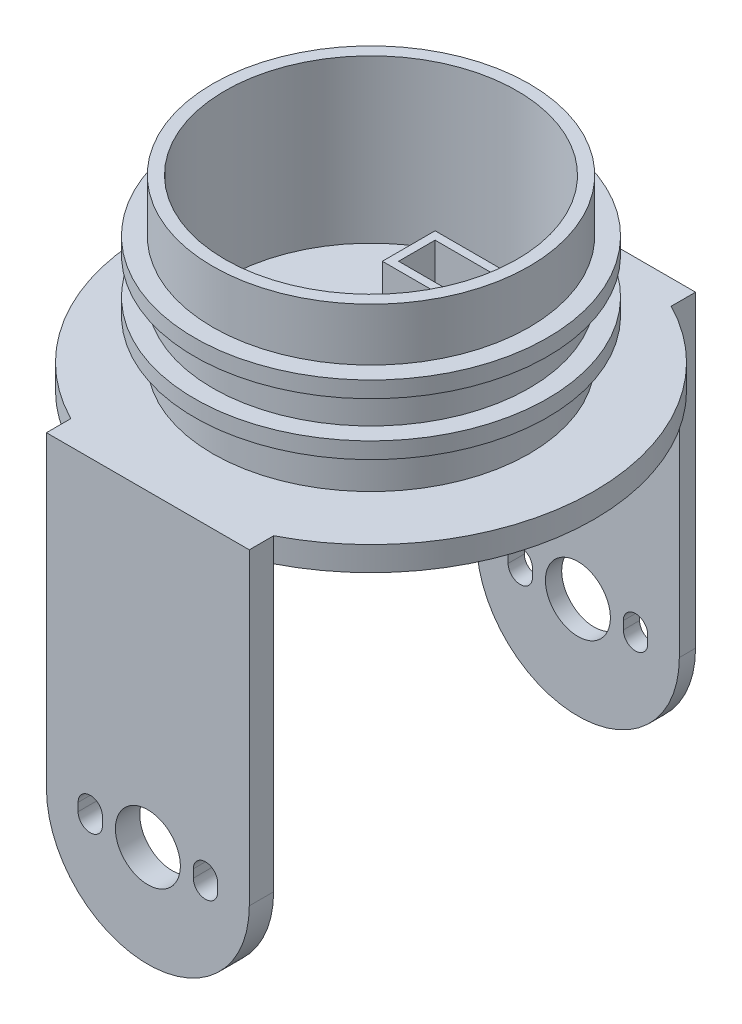
SolidWorks part; units mm, degrees
ref_plane "前基準面" through (0, 0, 0) normal (0, 0, 1) x (1, 0, 0)
ref_plane "上基準面" through (0, 0, 0) normal (0, 1, 0) x (1, 0, 0)
ref_plane "右基準面" through (0, 0, 0) normal (1, 0, 0) x (0, 0, -1)
sketch "草圖1" plane through (0, 0, 0) normal (0, 1, 0) x (1, 0, 0)
  circle A0 centre (0, 0) radius 19.5
  circle A1 centre (0, 0) radius 18
  dimension "D1" = 39
  dimension "D2" = 36
extrude "填料-伸長1" add sketch "草圖1" along normal blind 20
sketch "草圖3" plane through (0, 0, 0) normal (0, -1, 0) x (1, 0, 0)
  circle A0 centre (0, 0) radius 27.5
  dimension "D1" = 55
extrude "填料-伸長2" add sketch "草圖3" along normal blind 3
ref_plane "平面2" through (0, -3, 0) normal (0, -1, 0) x (-1, 0, 0)
ref_plane "平面5" through (0, 0, 0) normal (0, 1, 0) x (1, 0, 0)
ref_plane "平面6" through (0, 7, 0) normal (0, -1, 0) x (-1, 0, 0)
sketch "草圖25" plane through (0, 7, 0) normal (0, -1, 0) x (-1, 0, 0)
  circle A0 centre (0, 0) radius 21.75
  circle A1 centre (0, 0) radius 19.5
  dimension "D1" = 43.5
extrude "填料-伸長12" add sketch "草圖25" along normal blind 2
ref_plane "平面10" through (0, 10.5, 0) normal (0, -1, 0) x (-1, 0, 0)
sketch "草圖26" plane through (0, 10.5, 0) normal (0, -1, 0) x (-1, 0, 0)
  circle A0 centre (0, 0) radius 21.75
  circle A1 centre (0, 0) radius 19.5
extrude "填料-伸長13" add sketch "草圖26" against normal blind 2 from offset 1 offset against normal yes
sketch "草圖27" plane through (0, -3, 0) normal (0, -1, 0) x (1, 0, 0)
  line L0 (0, 0) -> (-12.5, 0)
  line L1 (46.0389, 0) -> (-46.0389, 0) construction
  line L2 (-12.5, 0) -> (-12.5, 25.5)
  line L3 (-12.5, 25.5) -> (12.5, 25.5)
  line L4 (12.5, 25.5) -> (12.5, 0)
  line L5 (12.5, 0) -> (-12.5, 0)
  line L6 (-12.5, 0) -> (-12.5, -25.5)
  line L7 (-12.5, -25.5) -> (12.5, -25.5)
  line L8 (12.5, -25.5) -> (12.5, 0)
  circle M6 centre (0, 0) radius 27.5
extrude "填料-伸長14" add sketch "草圖27" against normal blind 3 contours L8 L5 L0 L6 L7 M6 | L5 L4 L3 L2 L0 M6 | L6 L7 M6 | L7 L8 M6 | L4 L3 M6 | L3 L2 M6 region at (0, -3, -12.7084) region at (0, -3, 12.7084) region at (-11.7799, -3, 25.1714) region at (-11.7799, -3, -25.1714) region at (11.7799, -3, 25.1714) region at (11.7799, -3, -25.1714)
sketch "草圖28" plane through (0, 0, -25.5) normal (0, 0, -1) x (-1, 0, 0)
  line L0 (12.5, -3) -> (12.5, -38)
  line L1 (12.5, -38) -> (-12.5, -38)
  line L2 (-12.5, -38) -> (-12.5, 0)
  line L3 (-12.5, 0) -> (12.5, 0)
  line L4 (12.5, 0) -> (12.5, -3) construction
  line L5 (12.5, 0) -> (12.5, -3)
  line L6 (-7.1, -37.5) -> (-7.1, -38.5) construction
  line L7 (-5.6, -37.5) -> (-5.6, -38.5)
  line L8 (-8.6, -37.5) -> (-8.6, -38.5)
  line L9 (12.5, -3) -> (-12.5, -3)
  line L10 (7.1, -37.5) -> (7.1, -38.5) construction
  line L11 (8.6, -37.5) -> (8.6, -38.5)
  line L12 (5.6, -37.5) -> (5.6, -38.5)
  arc A0 (12.5, -38) -> (-12.5, -38) centre (0, -38) cw
  circle A1 centre (0, -38) radius 4
  arc A2 (-5.6, -37.5) -> (-8.6, -37.5) centre (-7.1, -37.5) ccw
  arc A3 (-8.6, -38.5) -> (-5.6, -38.5) centre (-7.1, -38.5) ccw
  arc A4 (8.6, -37.5) -> (5.6, -37.5) centre (7.1, -37.5) ccw
  arc A5 (5.6, -38.5) -> (8.6, -38.5) centre (7.1, -38.5) ccw
  point P14 (-7.1, -38)
  point P19 (-7.1, -36)
  point P20 (-7.1, -40)
  point P26 (7.1, -38)
  point P31 (7.1, -36)
  point P32 (7.1, -40)
  line M17 (10.2956, 0) -> (10.2956, -3)
  line M18 (10.2956, -3) -> (12.5, -3)
  line M19 (12.5, -3) -> (12.5, 0)
  line M20 (12.5, 0) -> (10.2956, 0)
  dimension "D1" = 8
  dimension "D2" = 4
  dimension "D3" = 3
  dimension "D4" = 5.6
  dimension "D5" = 4
  dimension "D6" = 3
  dimension "D7" = 5.6
  dimension "D8" = 35
extrude "填料-伸長17" add sketch "草圖28" along normal blind 2 contours A4 L11 L1 L0 L9 L2 L8 A2 L7 A1 L12 M18 | L9 L3 L2 M17 | M20 M17 M18 M19 | A5 L12 L1 A1 L7 A3 L8 A0 L11 region at (-11.3978, -1.5, -25.5) region at (0, -19.8277, -25.5) region at (0, -43.9487, -25.5) region at (1.1022, -1.5, -25.5)
extrude "填料-伸長19" add sketch "草圖28<15>" against normal blind 53 contours A4 L11 L1 L0 L9 L2 L8 A2 L7 A1 L12 M18 | A5 L12 L1 A1 L7 A3 L8 A0 L11 region at (0, -19.8277, -25.5) region at (0, -43.9487, -25.5)
sketch "草圖28<15>" plane through (0, 0, -25.5) normal (0, 0, -1) x (-1, 0, 0) same geometry as "草圖28"
sketch "草圖32" plane through (0, 0, 25.5) normal (0, 0, 1) x (1, 0, 0)
  line L0 (10.2956, -3) -> (12.5, -3)
  line L1 (-30.25, -3) -> (30.25, -3) construction
  line L2 (12.5, -3) -> (0, -3) construction
  line L3 (12.5, -3) -> (12.5, 0)
  line L4 (19.5, 0) -> (-19.5, 0) construction
  line L5 (12.5, 0) -> (12.5, -3) construction
  line L6 (12.5, 0) -> (10.2956, 0)
  line L7 (10.2956, 0) -> (10.2956, -3) construction
  line L8 (10.2956, 0) -> (10.2956, -3)
  line L9 (-10.2956, 0) -> (-10.2956, -3)
  line L10 (-10.2956, -3) -> (-10.2956, 0) construction
  line L11 (0, -3) -> (-12.5, -3) construction
  line L12 (-12.5, -3) -> (-10.2956, -3) construction
  line L13 (-10.2956, -3) -> (-12.5, -3)
  line L14 (-12.5, -3) -> (-12.5, 0)
  line L15 (-12.5, -3) -> (-12.5, 0) construction
  line L16 (-12.5, 0) -> (-10.2956, 0)
extrude "填料-伸長20" add sketch "草圖32" along normal blind 2
extrude "除料-伸長8" cut sketch "草圖28<18>" against normal blind 50 contours A4 L11 L1 L0 L9 L2 L8 A2 L7 A1 L12 M18 | A5 L12 L1 A1 L7 A3 L8 A0 L11 region at (0, -19.8277, -25.5) region at (0, -43.9487, -25.5)
sketch "草圖28<18>" plane through (0, 0, -25.5) normal (0, 0, -1) x (-1, 0, 0) same geometry as "草圖28"
sketch "草圖33" plane through (0, 0, 27.5) normal (0, 0, 1) x (1, 0, 0)
  line L0 (-12.5, -3) -> (12.5, -3)
  line L1 (-30.25, -3) -> (30.25, -3) construction
  line L2 (-12.5, -3) -> (-12.5, 0) construction
  line L3 (12.5, 0) -> (12.5, -3) construction
  line L4 (12.5, -3) -> (12.5, 0)
  line L5 (19.5, 0) -> (-19.5, 0) construction
  line L6 (12.5, 0) -> (-12.5, 0)
  line L7 (-12.5, 0) -> (-12.5, -3)
extrude "填料-伸長21" add sketch "草圖33" against normal blind 3
sketch "草圖34" plane through (0, 0, 0) normal (0, 1, 0) x (1, 0, 0)
  line L0 (0, 0) -> (-17.3838, 0) construction
  line L1 (-17.3838, 0) -> (19.1481, 0) construction
  line L2 (0, 0) -> (0, -21.2728) construction
  line L3 (0, -21.2728) -> (0, 19.1859) construction
  line L4 (5.1, 13) -> (-5.1, 13) construction
  line L5 (-4.1, 12) -> (4.1, 12)
  line L6 (-4.1, 12) -> (-4.1, 7.5)
  line L7 (-4.1, 7.5) -> (4.1, 7.5)
  line L8 (4.1, 12) -> (4.1, 7.5)
  line L10 (5.1, 6.5) -> (-5.1, 6.5)
  line L11 (5.1, 6.5) -> (5.1, 13)
  line L12 (5.1, 13) -> (-5.1, 13)
  line L13 (-5.1, 6.5) -> (-5.1, 13)
  point P13 (0, 13)
  dimension "D1" = 8.2
  dimension "D2" = 4.5
  dimension "D3" = 1
  dimension "D4" = 12
  dimension "D5" = 1
  dimension "D6" = 1
  dimension "D7" = 1
extrude "填料-伸長22" add sketch "草圖34" along normal blind 5
sketch "草圖37" plane through (0, 0, 0) normal (0, 1, 0) x (1, 0, 0)
  line L2 (-4.1, 12) -> (4.1, 12)
  line L3 (-4.1, 12) -> (-4.1, 7.5)
  line L4 (-4.1, 7.5) -> (4.1, 7.5)
  line L5 (4.1, 12) -> (4.1, 7.5)
extrude "除料-伸長9" cut sketch "草圖37" against normal blind 5
sketch "草圖38" plane through (0, 0, -27.5) normal (0, 0, -1) x (-1, 0, 0)
  line L0 (-27.5, -3) -> (27.5, -3) construction
  line L1 (0, -9.8) -> (-1, -14.4947) construction
  line L2 (-1, -14.4947) -> (-1.3125, -15.9618) construction
  line L3 (0, 0) -> (0, -50.5) construction
  line L4 (0, -9.8) -> (1, -14.4947) construction
  line L5 (1, -14.4947) -> (1.3125, -15.9618) construction
  line L6 (-1, -14.4947) -> (-1.3125, -15.9618)
  line L7 (1, -14.4947) -> (1.3125, -15.9618)
  arc A0 (-12.5, -38) -> (12.5, -38) centre (0, -38) ccw construction
  circle A2 centre (0, -9.8) radius 4.8
  circle A3 centre (0, -9.8) radius 6.3
  arc A4 (1, -14.4947) -> (-1, -14.4947) centre (0, -9.8) ccw
  dimension "D1" = 6.8
  dimension "D2" = 9.6
  dimension "D3" = 12.6
  dimension "D4" = 2
  dimension "D5" = 1
extrude "填料-伸長23" add sketch "草圖38" against normal blind 8 contours L7 A3 L6 A2 | L6 A3 L7 A2 region at (0, -15.3429, -27.5) region at (1.3296, -15.1913, -27.5)
extrude "除料-伸長10" cut sketch "草圖38<3>" against normal blind 9.5 contours A2 region at (0, -9.8, -27.5)
sketch "草圖38<3>" plane through (0, 0, -27.5) normal (0, 0, -1) x (-1, 0, 0) same geometry as "草圖38"
extrude "填料-伸長24" add sketch "草圖38<4>" along normal blind 3 contours L7 A3 L6 A2 region at (1.3296, -15.1913, -27.5)
sketch "草圖38<4>" plane through (0, 0, -27.5) normal (0, 0, -1) x (-1, 0, 0) same geometry as "草圖38"
